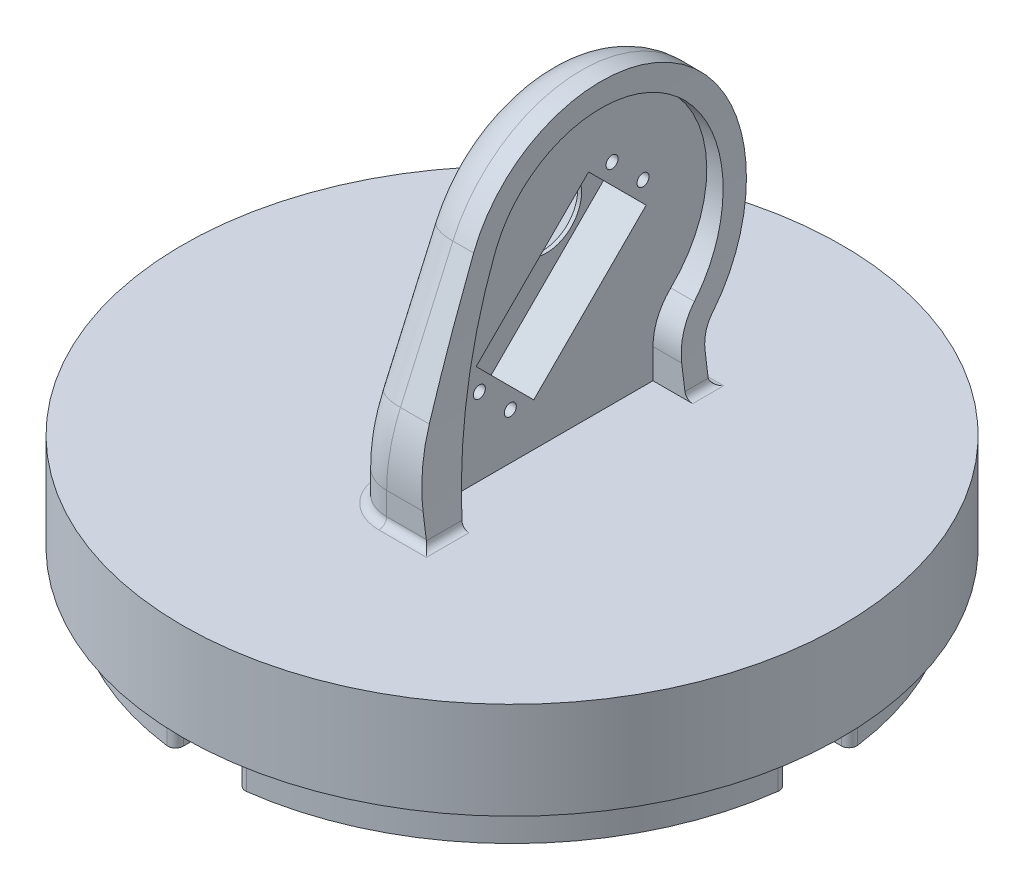
SolidWorks part; units mm, degrees
ref_plane "Front Plane" through (0, 0, 0) normal (0, 0, 1) x (1, 0, 0)
ref_plane "Top Plane" through (0, 0, 0) normal (0, 1, 0) x (1, 0, 0)
ref_plane "Right Plane" through (0, 0, 0) normal (1, 0, 0) x (0, 0, -1)
sketch "Sketch1" plane through (0, 0, 0) normal (0, 1, 0) x (1, 0, 0)
  circle A0 centre (0, 0) radius 85
  dimension "D1" = 170
extrude "Boss-Extrude1" add sketch "Sketch1" along normal blind 25
sketch "Sketch2" plane through (0, 0, 0) normal (0, -1, 0) x (1, 0, 0)
  line B0 (0, 0) -> (0, 85) construction
  line B1 (0, 0) -> (85, 0) construction
  line B2 (-7.9378, 79.1027) -> (-7.9434, 72.0635)
  line B3 (-79.1027, -7.9378) -> (-72.0635, -7.9434)
  line B4 (8.0622, 79.0901) -> (8.0566, 72.051)
  line B5 (-79.0901, 8.0622) -> (-72.051, 8.0566)
  line B6 (72.0635, 7.9434) -> (79.1027, 7.9378)
  line B7 (72.051, -8.0566) -> (79.0901, -8.0622)
  line B8 (7.9434, -72.0635) -> (7.9378, -79.1027)
  line B9 (-8.0566, -72.051) -> (-8.0622, -79.0901)
  arc B10 (-7.9378, 79.1027) -> (-79.0901, 8.0622) centre (0, 0) ccw
  arc B11 (-7.9434, 72.0635) -> (-72.051, 8.0566) centre (0, 0) ccw
  arc B12 (72.0635, 7.9434) -> (8.0566, 72.051) centre (0, 0) ccw
  arc B13 (79.1027, 7.9378) -> (8.0622, 79.0901) centre (0, 0) ccw
  arc B14 (-72.0635, -7.9434) -> (-8.0566, -72.051) centre (0, 0) ccw
  arc B15 (-79.1027, -7.9378) -> (-8.0622, -79.0901) centre (0, 0) ccw
  arc B16 (7.9434, -72.0635) -> (72.051, -8.0566) centre (0, 0) ccw
  arc B17 (7.9378, -79.1027) -> (79.0901, -8.0622) centre (0, 0) ccw
  circle B18 centre (0, 0) radius 79.5 construction
sketch_block_instance "Block1-1"
sketch_block "Block1" parameters "D1"=159, "D2"=7, "D3"=16, "D4"=16, "D5"=16, "D6"=8, "D7"=8, "D8"=8, "D9"=0.045, "D10"=90, "D11"=90
extrude "Boss-Extrude2" add sketch "Sketch2" along normal blind 10
fillet "Fillet1" radius 2 16 edges at (8.0622, -5, 79.0901) (8.0566, -5, 72.051) (72.0635, -5, 7.9434) (79.1027, -5, 7.9378) (72.051, -5, -8.0566) (79.0901, -5, -8.0622) (7.9378, -5, -79.1027) (7.9434, -5, -72.0635) (-8.0566, -5, -72.051) (-72.0635, -5, -7.9434) (-8.0622, -5, -79.0901) (-79.1027, -5, -7.9378) (-79.0901, -5, 8.0622) (-72.051, -5, 8.0566) (-7.9434, -5, 72.0635) (-7.9378, -5, 79.1027)
ref_plane "Plane1" through (0, 0, 0) normal (1, 0, 0) x (0, 0, -1)
sketch "Sketch3" plane through (0, 0, 0) normal (1, 0, 0) x (0, 0, -1)
  line L0 (30.34, 25) -> (-30.34, 25)
  line L1 (85, 25) -> (-85, 25) construction
  line L2 (30.34, 25) -> (30.34, 32.64)
  line L3 (-30.34, 25) -> (-30.34, 32.86)
  line L4 (-27.3064, 47.162) -> (-13.7928, 77.5835)
  arc A0 (30.34, 32.64) -> (34.9351, 43.4445) centre (45.34, 32.64) cw
  arc A1 (34.9351, 43.4445) -> (-13.7928, 77.5835) centre (13.9089, 65.2782) ccw
  arc A2 (-30.34, 32.86) -> (-27.3064, 47.162) centre (4.89, 32.86) cw
  circle A3 centre (13.9089, 65.2782) radius 9
  point P5 (0, 25)
  dimension "D3" = 15
  dimension "D4" = 7.86
  dimension "D5" = 35.23
  dimension "D6" = 18
  dimension "D1" = 60.68
  dimension "D2" = 7.64
  dimension "D7" = 13.9089
  dimension "D8" = 40.2782
extrude "Boss-Extrude3" add sketch "Sketch3" along normal mid plane 12
sketch "Sketch4" plane through (6, 0, 0) normal (1, 0, 0) x (0, 0, -1)
  line L0 (-0.41, 36.11) -> (28.5814, 65.1014)
  line L1 (-0.41, 36.11) -> (-15.2592, 50.9592)
  line L2 (28.5814, 65.1014) -> (13.7321, 79.9506)
  line L3 (-15.2592, 50.9592) -> (13.7321, 79.9506)
  line L4 (-0.41, 36.11) -> (13.7321, 79.9506) construction
  line L5 (28.5814, 65.1014) -> (-15.2592, 50.9592) construction
  line L6 (-30.34, 25) -> (30.34, 25) construction
  line L7 (-0.7636, 65.4549) -> (14.0857, 50.6057) construction
  line L8 (6.6611, 58.0303) -> (23.7731, 75.1423) construction
  line L9 (27.7682, 71.1471) -> (19.7779, 79.1374) construction
  line L20 (14.3332, 78.996) -> (27.6268, 65.7024)
  line L21 (27.6268, 65.7024) -> (31.8341, 69.9097)
  line L22 (31.8341, 71.3239) -> (30.7027, 72.4553)
  line L23 (30.7027, 72.4553) -> (29.8659, 71.6185)
  line L24 (28.2396, 73.2448) -> (29.0764, 74.0816)
  line L25 (29.0764, 74.0816) -> (22.7124, 80.4456)
  line L26 (22.7124, 80.4456) -> (21.8756, 79.6088)
  line L27 (20.2492, 81.2351) -> (21.086, 82.0719)
  line L28 (21.086, 82.0719) -> (19.9032, 83.2548)
  line L29 (18.489, 83.2548) -> (14.2779, 79.0438)
  line L30 (14.3332, 78.996) -> (27.6268, 65.7024)
  line L31 (27.6268, 65.7024) -> (31.8341, 69.9097)
  line L32 (31.8341, 71.3239) -> (30.7027, 72.4553)
  line L33 (30.7027, 72.4553) -> (29.8659, 71.6185)
  line L34 (28.2396, 73.2448) -> (29.0764, 74.0816)
  line L35 (29.0764, 74.0816) -> (22.7124, 80.4456)
  line L36 (22.7124, 80.4456) -> (21.8756, 79.6088)
  line L37 (20.2492, 81.2351) -> (21.086, 82.0719)
  line L38 (21.086, 82.0719) -> (19.9032, 83.2548)
  line L39 (18.489, 83.2548) -> (14.2779, 79.0438)
  circle A0 centre (27.7682, 71.1471) radius 1.55
  circle A1 centre (19.7779, 79.1374) radius 1.55
  circle A2 centre (-14.4461, 44.9135) radius 1.55
  circle A3 centre (-6.4558, 36.9232) radius 1.55
  arc A14 (14.3332, 78.996) -> (14.2779, 79.0438) centre (13.9796, 78.6425) ccw
  arc A15 (14.3332, 78.996) -> (14.2779, 79.0438) centre (13.9796, 78.6425) ccw
  arc A16 (31.8341, 69.9097) -> (31.8341, 71.3239) centre (31.127, 70.6168) ccw
  arc A17 (31.8341, 69.9097) -> (31.8341, 71.3239) centre (31.127, 70.6168) ccw
  arc A18 (28.2396, 73.2448) -> (29.8659, 71.6185) centre (27.7682, 71.1471) ccw
  arc A19 (28.2396, 73.2448) -> (29.8659, 71.6185) centre (27.7682, 71.1471) ccw
  arc A20 (20.2492, 81.2351) -> (21.8756, 79.6088) centre (19.7779, 79.1374) ccw
  arc A21 (20.2492, 81.2351) -> (21.8756, 79.6088) centre (19.7779, 79.1374) ccw
  arc A22 (19.9032, 83.2548) -> (18.489, 83.2548) centre (19.1961, 82.5477) ccw
  arc A23 (19.9032, 83.2548) -> (18.489, 83.2548) centre (19.1961, 82.5477) ccw
  point P1 (6.6611, 58.0303)
  point P15 (23.7731, 75.1423)
  dimension "D8" = 3.1
  dimension "D6" = 0
  dimension "D1" = 0.41
  dimension "D2" = 11.11
  dimension "D3" = 21
  dimension "D4" = 41
  dimension "D5" = 45
extrude "Cut-Extrude1" cut sketch "Sketch4" along normal through all both and the other way through all from offset 6 contours A0 | A1 | A3 | A2 region at (6, 71.1471, -27.7682) region at (6, 79.1374, -19.7779) region at (6, 44.9135, 14.4461) region at (6, 36.9232, 6.4558) offset against normal yes
sketch "Sketch7" plane through (6, 0, 0) normal (1, 0, 0) x (0, 0, -1)
  line L0 (33.34, 25) -> (33.34, 32.64) construction
  line L1 (-16.5345, 78.8014) -> (-30.0481, 48.3798) construction
  line L2 (-33.34, 32.86) -> (-33.34, 25) construction
  line L3 (36.34, 25) -> (36.34, 32.64)
  line L4 (-30.34, 32.86) -> (-30.34, 25)
  line L5 (-30.34, 25) -> (30.34, 25)
  line L6 (30.34, 25) -> (30.34, 32.64)
  line L7 (-13.7928, 77.5835) -> (-27.3064, 47.162)
  line L8 (-30.34, 32.86) -> (-30.34, 25) construction
  line L10 (30.34, 25) -> (30.34, 32.64)
  line L11 (-13.7928, 77.5835) -> (-27.3064, 47.162) construction
  line L12 (-19.2761, 80.0193) -> (-32.7897, 49.5977)
  line L13 (-36.34, 32.86) -> (-36.34, 25)
  line L14 (85, 25) -> (-85, 25) construction
  line L15 (-36.34, 25) -> (-27.34, 25)
  line L16 (30.34, 25) -> (36.34, 25)
  arc A0 (37.0161, 41.2836) -> (33.34, 32.64) centre (45.34, 32.64) ccw construction
  arc A1 (37.0161, 41.2836) -> (-16.5345, 78.8014) centre (13.9089, 65.2782) ccw construction
  arc A2 (-30.0481, 48.3798) -> (-33.34, 32.86) centre (4.89, 32.86) ccw construction
  arc A3 (34.9351, 43.4445) -> (30.34, 32.64) centre (45.34, 32.64) ccw
  arc A4 (34.9351, 43.4445) -> (-13.7928, 77.5835) centre (13.9089, 65.2782) ccw
  arc A5 (-27.3064, 47.162) -> (-30.34, 32.86) centre (4.89, 32.86) ccw
  arc A6 (34.9351, 43.4445) -> (30.34, 32.64) centre (45.34, 32.64) ccw
  arc A7 (34.9351, 43.4445) -> (-13.7928, 77.5835) centre (13.9089, 65.2782) ccw
  arc A8 (-27.3064, 47.162) -> (-30.34, 32.86) centre (4.89, 32.86) ccw construction
  arc A9 (39.097, 39.1227) -> (36.34, 32.64) centre (45.34, 32.64) ccw
  arc A10 (39.097, 39.1227) -> (-19.2761, 80.0193) centre (13.9089, 65.2782) ccw
  arc A11 (-32.7897, 49.5977) -> (-36.34, 32.86) centre (4.89, 32.86) ccw
  arc A12 (-13.7928, 77.5835) -> (-27.34, 25) centre (136.4758, 10.8327) ccw
  dimension "D4" = 3
  dimension "D5" = 164.4273
  dimension "D2" = 3
  dimension "D3" = 3
  dimension "D1" = 0
extrude "Boss-Extrude5" add sketch "Sketch7" along normal blind 9 and the other way up to surface (12 mm away) other way up to face at (-6, 71.1471, -26.2182)
sketch "Sketch8" plane through (0, 0, 0) normal (0, 0, 1) x (1, 0, 0)
  line L0 (15, 101.59) -> (9, 101.59)
  line L5 (-6, 25) -> (15, 25) construction
  line L6 (14.5, 25) -> (15, 25)
  line L7 (15, 25) -> (15, 101.59)
  arc A1 (9, 101.59) -> (14.5, 25) centre (508.9933, 99.0025) ccw
  dimension "D1" = 6
  dimension "D3" = 500
  dimension "D2" = 0.5
extrude "Cut-Extrude9" cut sketch "Sketch8" against normal through all both and the other way through all
fillet "Fillet3" radius 10 6 edges at (-6, 28.82, -36.34) (-6, 36.1623, -37.0579) (-6, 28.93, 36.34) (-6, 41.4151, 35.4427) (-6, 64.8085, 26.0329) (-6, 95.0175, -34.7445)
fillet "Fillet4" radius 2 5 edges at (9.25, 25, 36.34) (-3.0711, 25, 33.4111) (9.25, 25, -36.34) (-3.0711, 25, -33.4111) (-6, 25, 0)
fillet "Fillet5" radius 2 2 edges at (14.5, 25, -34.34) (14.5, 25, 32.84)
extrude "Cut-Extrude11" cut sketch "Sketch4<3>" against normal blind 11 contours L1 L3 L2 L0
sketch "Sketch4<3>" plane through (6, 0, 0) normal (1, 0, 0) x (0, 0, -1) same geometry as "Sketch4"
